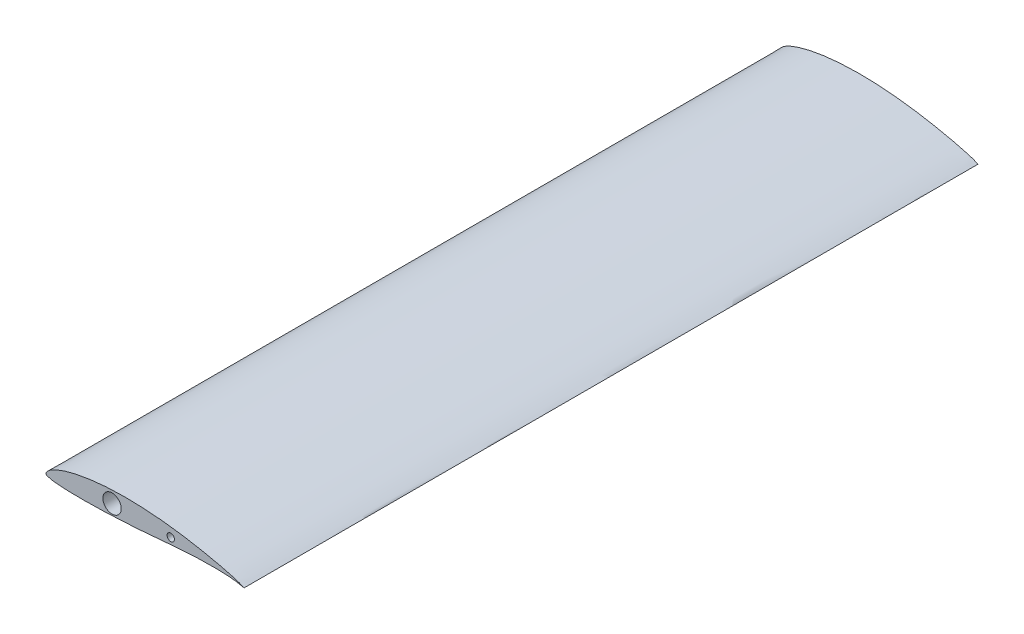
SolidWorks part; units mm, degrees
material "polystirene foam"
ref_plane "Front Plane" through (0, 0, 0) normal (0, 0, 1) x (1, 0, 0)
ref_plane "Top Plane" through (0, 0, 0) normal (0, 1, 0) x (1, 0, 0)
ref_plane "Right Plane" through (0, 0, 0) normal (1, 0, 0) x (0, 0, -1)
curve "Curve1"
  spline degree 3 poles (267.933, 0.5337, 0) (270.49, -0.1564, 0) (268.2375, 0.6665, 0) (266.5672, 1.4668, 0) (262.6756, 3.0154, 0) (257.9132, 4.5724, 0) (251.732, 6.3325, 0) (244.4112, 8.2376, 0) (235.9576, 10.2728, 0) (226.5142, 12.3893, 0) (216.1934, 14.5409, 0) (205.1313, 16.6775, 0) (193.4567, 18.7298, 0) (181.2977, 20.6324, 0) (168.7678, 22.3117, 0) (155.9753, 23.7079, 0) (143.0353, 24.8049, 0) (130.0617, 25.5802, 0) (117.1734, 26.0003, 0) (104.4837, 26.0576, 0) (92.1044, 25.7531, 0) (80.1395, 25.0742, 0) (68.69, 24.0381, 0) (57.8509, 22.6699, 0) (47.7143, 21.0125, 0) (38.3732, 19.0872, 0) (29.9084, 16.9558, 0) (22.399, 14.6444, 0) (15.9079, 12.2159, 0) (10.4843, 9.7202, 0) (6.177, 7.2209, 0) (2.9612, 4.7412, 0) (0.9766, 2.4261, 0) (0.0237, 0.7907, 0) (-0.0162, -0.4697, 0) (0.8003, -1.8361, 0) (3.4921, -2.6295, 0) (7.308, -3.6627, 0) (12.6566, -4.3991, 0) (19.3194, -5.0329, 0) (27.2905, -5.4698, 0) (36.4622, -5.7387, 0) (46.7414, -5.84, 0) (58.0105, -5.7702, 0) (70.1434, -5.5368, 0) (83.0071, -5.1408, 0) (96.4629, -4.5659, 0) (110.374, -3.827, 0) (124.6167, -2.893, 0) (139.0995, -1.7363, 0) (153.7348, -0.4008, 0) (168.4097, 0.8923, 0) (182.9339, 2.0414, 0) (197.0782, 2.9592, 0) (210.6044, 3.579, 0) (223.2667, 3.8744, 0) (234.8405, 3.8186, 0) (245.0477, 3.4533, 0) (253.7786, 2.7629, 0) (260.4407, 1.9422, 0) (265.7815, 0.9299, 0) (267.933, 0.5337, 0) (270.49, -0.1564, 0) (268.2375, 0.6665, 0) knots -0.016249 -0.007187 -0.001789 0 0.001694 0.006395 0.013462 0.022754 0.034367 0.048191 0.064031 0.081681 0.100894 0.121432 0.143025 0.165434 0.188439 0.211855 0.235496 0.259144 0.282615 0.305702 0.328232 0.35003 0.370944 0.390817 0.409506 0.426857 0.442733 0.457018 0.469615 0.48045 0.489472 0.49673 0.502329 0.506256 0.506442 0.509182 0.513914 0.521178 0.530944 0.543145 0.55767 0.574384 0.59311 0.613638 0.635744 0.659184 0.683714 0.709076 0.735036 0.76143 0.788184 0.815057 0.841645 0.867514 0.892232 0.915364 0.936485 0.9552 0.971104 0.983751 0.992813 0.998211 1 1.001694 1.006395 1.013462 periodic
sketch "Sketch1" plane through (0, 0, 0) normal (0, 0, 1) x (1, 0, 0)
  line L0 (270, 0) -> (0, 0) construction
  line L1 (0, -23.2448) -> (0, 51.8173) construction
  line L2 (90, 9.6033) -> (90, 0) construction
  line L3 (0, 26.0183) -> (162.1091, 26.0183) construction
  line L4 (0, -5.812) -> (132.6055, -5.812) construction
  circle A0 centre (90, 9.6033) radius 12.5
  circle A1 centre (170, 9.6033) radius 5
  spline S0 degree 3 poles (267.933, 0.5337) (270.49, -0.1564) (268.2375, 0.6665) (266.5672, 1.4668) (262.6756, 3.0154) (257.9132, 4.5724) (251.732, 6.3325) (244.4112, 8.2376) (235.9576, 10.2728) (226.5142, 12.3893) (216.1934, 14.5409) (205.1313, 16.6775) (193.4567, 18.7298) (181.2977, 20.6324) (168.7678, 22.3117) (155.9753, 23.7079) (143.0353, 24.8049) (130.0617, 25.5802) (117.1734, 26.0003) (104.4837, 26.0576) (92.1044, 25.7531) (80.1395, 25.0742) (68.69, 24.0381) (57.8509, 22.6699) (47.7143, 21.0125) (38.3732, 19.0872) (29.9084, 16.9558) (22.399, 14.6444) (15.9079, 12.2159) (10.4843, 9.7202) (6.177, 7.2209) (2.9612, 4.7412) (0.9766, 2.4261) (0.0237, 0.7907) (-0.0162, -0.4697) (0.8003, -1.8361) (3.4921, -2.6295) (7.308, -3.6627) (12.6566, -4.3991) (19.3194, -5.0329) (27.2905, -5.4698) (36.4622, -5.7387) (46.7414, -5.84) (58.0105, -5.7702) (70.1434, -5.5368) (83.0071, -5.1408) (96.4629, -4.5659) (110.374, -3.827) (124.6167, -2.893) (139.0995, -1.7363) (153.7348, -0.4008) (168.4097, 0.8923) (182.9339, 2.0414) (197.0782, 2.9592) (210.6044, 3.579) (223.2667, 3.8744) (234.8405, 3.8186) (245.0477, 3.4533) (253.7786, 2.7629) (260.4407, 1.9422) (265.7815, 0.9299) (267.933, 0.5337) (270.49, -0.1564) (268.2375, 0.6665) knots -0.016249 -0.007187 -0.001789 0 0.001694 0.006395 0.013462 0.022754 0.034367 0.048191 0.064031 0.081681 0.100894 0.121432 0.143025 0.165434 0.188439 0.211855 0.235496 0.259144 0.282615 0.305702 0.328232 0.35003 0.370944 0.390817 0.409506 0.426857 0.442733 0.457018 0.469615 0.48045 0.489472 0.49673 0.502329 0.506256 0.506442 0.509182 0.513914 0.521178 0.530944 0.543145 0.55767 0.574384 0.59311 0.613638 0.635744 0.659184 0.683714 0.709076 0.735036 0.76143 0.788184 0.815057 0.841645 0.867514 0.892232 0.915364 0.936485 0.9552 0.971104 0.983751 0.992813 0.998211 1 1.001694 1.006395 1.013462 only from (270, 0) to (270, 0) construction
  spline S1 degree 3 poles (267.933, 0.5337) (270.49, -0.1564) (268.2375, 0.6665) (266.5672, 1.4668) (262.6756, 3.0154) (257.9132, 4.5724) (251.732, 6.3325) (244.4112, 8.2376) (235.9576, 10.2728) (226.5142, 12.3893) (216.1934, 14.5409) (205.1313, 16.6775) (193.4567, 18.7298) (181.2977, 20.6324) (168.7678, 22.3117) (155.9753, 23.7079) (143.0353, 24.8049) (130.0617, 25.5802) (117.1734, 26.0003) (104.4837, 26.0576) (92.1044, 25.7531) (80.1395, 25.0742) (68.69, 24.0381) (57.8509, 22.6699) (47.7143, 21.0125) (38.3732, 19.0872) (29.9084, 16.9558) (22.399, 14.6444) (15.9079, 12.2159) (10.4843, 9.7202) (6.177, 7.2209) (2.9612, 4.7412) (0.9766, 2.4261) (0.0237, 0.7907) (-0.0162, -0.4697) (0.8003, -1.8361) (3.4921, -2.6295) (7.308, -3.6627) (12.6566, -4.3991) (19.3194, -5.0329) (27.2905, -5.4698) (36.4622, -5.7387) (46.7414, -5.84) (58.0105, -5.7702) (70.1434, -5.5368) (83.0071, -5.1408) (96.4629, -4.5659) (110.374, -3.827) (124.6167, -2.893) (139.0995, -1.7363) (153.7348, -0.4008) (168.4097, 0.8923) (182.9339, 2.0414) (197.0782, 2.9592) (210.6044, 3.579) (223.2667, 3.8744) (234.8405, 3.8186) (245.0477, 3.4533) (253.7786, 2.7629) (260.4407, 1.9422) (265.7815, 0.9299) (267.933, 0.5337) (270.49, -0.1564) (268.2375, 0.6665) knots -0.016249 -0.007187 -0.001789 0 0.001694 0.006395 0.013462 0.022754 0.034367 0.048191 0.064031 0.081681 0.100894 0.121432 0.143025 0.165434 0.188439 0.211855 0.235496 0.259144 0.282615 0.305702 0.328232 0.35003 0.370944 0.390817 0.409506 0.426857 0.442733 0.457018 0.469615 0.48045 0.489472 0.49673 0.502329 0.506256 0.506442 0.509182 0.513914 0.521178 0.530944 0.543145 0.55767 0.574384 0.59311 0.613638 0.635744 0.659184 0.683714 0.709076 0.735036 0.76143 0.788184 0.815057 0.841645 0.867514 0.892232 0.915364 0.936485 0.9552 0.971104 0.983751 0.992813 0.998211 1 1.001694 1.006395 1.013462 only from (270, 0) to (270, 0)
  dimension "D1" = 25
  dimension "D6" = 10
  dimension "D2" = 90
  dimension "D3" = 31.8303
  dimension "D4" = 16.415
  dimension "D5" = 80
extrude "Boss-Extrude1" add sketch "Sketch1" along normal blind 1000 contours S1
extrude "Cut-Extrude1" cut sketch "Sketch1<3>" along normal through all contours A0 | A1
sketch "Sketch1<3>" plane through (0, 0, 0) normal (0, 0, 1) x (1, 0, 0) same geometry as "Sketch1"
